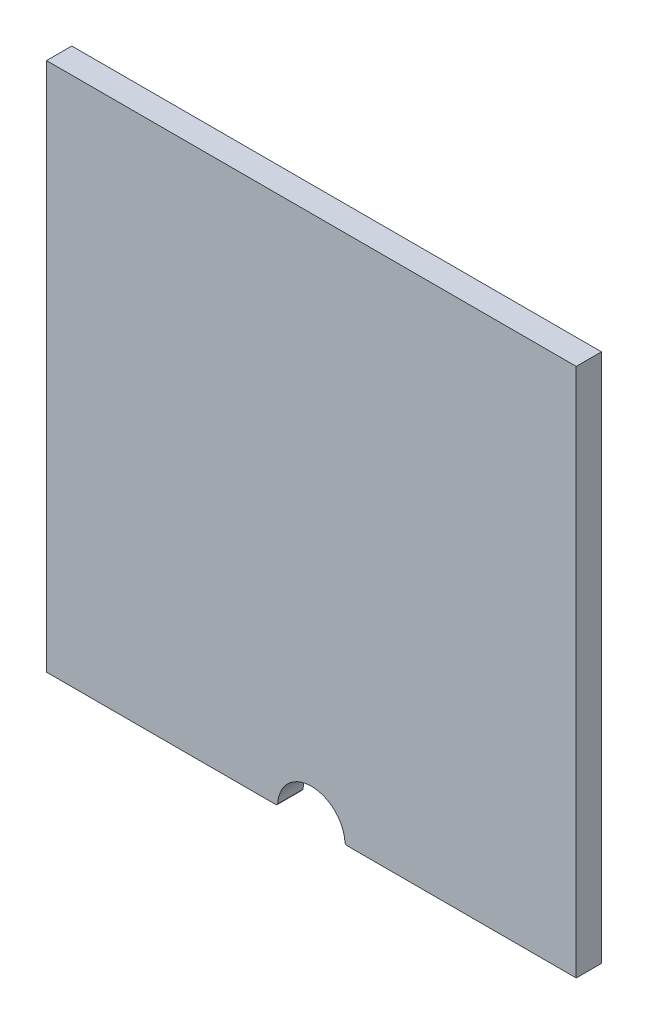
SolidWorks part; units mm, degrees
material "NEOPRENE"
ref_plane "Front Plane" through (0, 0, 0) normal (0, 0, 1) x (1, 0, 0)
ref_plane "Top Plane" through (0, 0, 0) normal (0, 1, 0) x (1, 0, 0)
ref_plane "Right Plane" through (0, 0, 0) normal (1, 0, 0) x (0, 0, -1)
sketch "Sketch1" plane through (0, 0, 0) normal (0, 0, 1) x (1, 0, 0)
  line L1 (0, 0) -> (200, 0)
  line L2 (0, 0) -> (0, 200)
  line L3 (0, 200) -> (200, 200)
  line L4 (200, 0) -> (200, 200)
  dimension "D1" = 200
extrude "Boss-Extrude1" add sketch "Sketch1" along normal blind 9.525
sketch "Sketch5" plane through (0, 0, 9.525) normal (0, 0, 1) x (1, 0, 0)
  line L0 (200, 0) -> (200, 200) construction
  line L1 (0, 0) -> (200, 0) construction
  line L2 (0, 200) -> (0, 0) construction
  line L3 (200, 200) -> (0, 200) construction
  line L4 (200, 0) -> (200, 200)
  line L5 (0, 0) -> (200, 0)
  line L6 (0, 200) -> (0, 0)
  line L7 (200, 200) -> (0, 200)
  line L8 (199.9492, 0.0508) -> (199.9492, 199.9492)
  line L9 (199.9492, 199.9492) -> (0.0508, 199.9492)
  line L10 (0.0508, 199.9492) -> (0.0508, 0.0508)
  line L11 (0.0508, 0.0508) -> (199.9492, 0.0508)
  dimension "D1" = 0.0508
extrude "Cut-Extrude2" cut sketch "Sketch5" against normal through all
sketch "Sketch2" plane through (0, 0, 9.525) normal (0, 0, 1) x (1, 0, 0)
  line L1 (87.3, 0.0508) -> (112.7, 0.0508)
  line L2 (0.0508, 0.0508) -> (199.9492, 0.0508) construction
  line L3 (100, 199.9492) -> (100, 0.0508) construction
  line L4 (199.9492, 199.9492) -> (0.0508, 199.9492) construction
  arc A0 (112.7, 0.0508) -> (87.3, 0.0508) centre (100, 0.0508) ccw
  dimension "D1" = 25.4
extrude "Cut-Extrude1" cut sketch "Sketch2" against normal blind 9.525
fillet "Fillet1" radius 0.7937 2 edges at (87.3, 0.0508, 4.7625) (112.7, 0.0508, 4.7625)
sketch "Sketch6" plane through (0, 0, 9.525) normal (0, 0, 1) x (1, 0, 0)
  line L0 (0.0508, 199.9492) -> (0.0508, 0.0508) construction
  line L1 (0.0508, 0.0508) -> (86.5296, 0.0508) construction
  circle A0 centre (2.0828, 2.0828) radius 0.7938
  dimension "D1" = 1.5875
  dimension "D2" = 2.032
  dimension "D3" = 2.032
extrude "Cut-Extrude3" [suppressed] cut sketch "Sketch6" against normal blind 1.27
pattern_linear "LPattern1" [suppressed] count 4 spacing 2.54 of bodies 104
